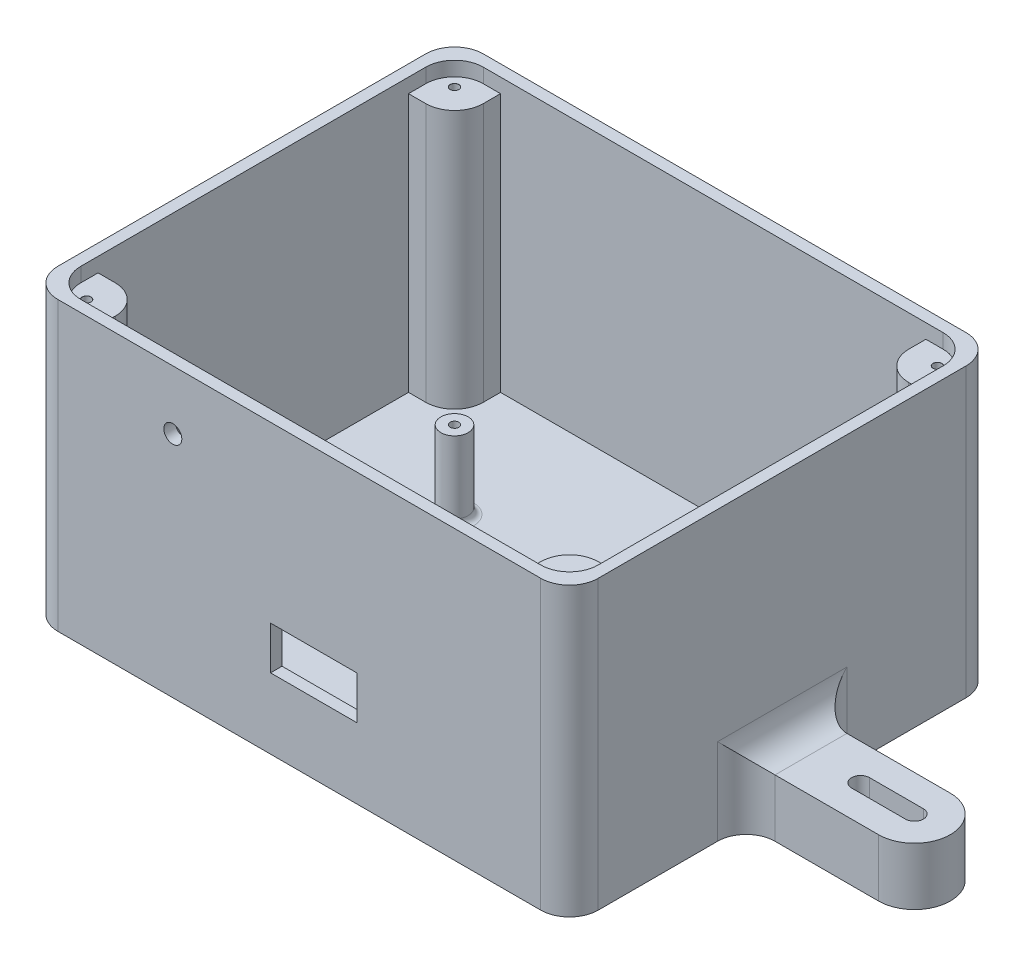
SolidWorks part; units mm, degrees
ref_plane "Plano frontal" through (0, 0, 0) normal (0, 0, 1) x (1, 0, 0)
ref_plane "Plano superior" through (0, 0, 0) normal (0, 1, 0) x (1, 0, 0)
ref_plane "Plano direito" through (0, 0, 0) normal (1, 0, 0) x (0, 0, -1)
ref_plane "Plano1" through (0, 0, -4.75) normal (0, 0, 1) x (1, 0, 0)
sketch "Esboço1" plane through (0, 0, -4.75) normal (0, 0, 1) x (1, 0, 0)
  line L0 (100, 27) -> (95.25, 27)
  line L1 (95.25, 27) -> (95.25, 26)
  line L2 (95.25, 26) -> (100, 26)
  line L3 (100, 26) -> (100, 27)
  line L4 (95.25, 27) -> (95.25, 26) construction
revolve "Revolução1" add sketch "Esboço1" angle 180 about L4 reverse direction yes
sketch "Esboço2" plane through (0, 0, -4.75) normal (0, 0, 1) x (1, 0, 0)
  line L0 (90.5, 100) -> (100, 100)
  line L1 (100, 100) -> (100, 26)
  line L2 (100, 26) -> (90.5, 26)
  line L3 (90.5, 26) -> (90.5, 100)
extrude "Ressalto-extrusão1" add sketch "Esboço2" along normal blind 8.75
sketch "Esboço3" plane through (90.5, 0, 0) normal (-1, 0, 0) x (0, 0, 1)
  line L0 (-4.75, 27) -> (4, 27)
  line L1 (4, 27) -> (4, 100)
  line L2 (4, 100) -> (-4.75, 100)
  line L3 (-4.75, 100) -> (-4.75, 27)
extrude "Corte-extrusão1" cut sketch "Esboço3" against normal blind 1.5
sketch "Esboço4" plane through (0, 0, -4.75) normal (0, 0, -1) x (-1, 0, 0)
  line L0 (-92, 27) -> (-92, 100)
  line L1 (-92, 100) -> (-100, 100)
  line L2 (-100, 100) -> (-100, 27)
  line L3 (-100, 27) -> (-92, 27)
extrude "Corte-extrusão2" cut sketch "Esboço4" against normal blind 4.75
sketch "Esboço5" plane through (92, 0, 0) normal (-1, 0, 0) x (0, 0, 1)
  line L0 (4, 32) -> (0, 32)
  line L1 (0, 32) -> (0, 100)
  line L2 (0, 100) -> (4, 100)
  line L3 (4, 100) -> (4, 32)
extrude "Ressalto-extrusão2" add sketch "Esboço5" along normal blind 52
sketch "Esboço6" plane through (40, 0, 0) normal (-1, 0, 0) x (0, 0, 1)
  line L0 (4, 26) -> (0, 26)
  line L1 (0, 26) -> (0, 100)
  line L2 (0, 100) -> (4, 100)
  line L3 (4, 100) -> (4, 26)
extrude "Ressalto-extrusão3" add sketch "Esboço6" along normal blind 80
sketch "Esboço7" plane through (100, 0, 0) normal (1, 0, 0) x (0, 0, -1)
  line L0 (0, 100) -> (0, 26)
  line L1 (0, 26) -> (-4, 26)
  line L2 (-4, 26) -> (-4, 100)
  line L3 (-4, 100) -> (0, 100)
extrude "Ressalto-extrusão4" add sketch "Esboço7" along normal blind 40
sketch "Esboço8" plane through (140, 0, 0) normal (1, 0, 0) x (0, 0, -1)
  line L0 (140, 26) -> (-4, 26)
  line L1 (-4, 26) -> (-4, 100)
  line L2 (-4, 100) -> (140, 100)
  line L3 (140, 100) -> (140, 26)
extrude "Ressalto-extrusão5" add sketch "Esboço8" along normal blind 4
sketch "Esboço9" plane through (-40, 0, 0) normal (-1, 0, 0) x (0, 0, 1)
  line L0 (-140, 26) -> (-140, 100)
  line L1 (-140, 100) -> (4, 100)
  line L2 (4, 100) -> (4, 26)
  line L3 (4, 26) -> (-140, 26)
extrude "Ressalto-extrusão6" add sketch "Esboço9" along normal blind 4
sketch "Esboço10" plane through (0, 0, -140) normal (0, 0, -1) x (-1, 0, 0)
  line L0 (-144, 26) -> (-144, 100)
  line L1 (-144, 100) -> (44, 100)
  line L2 (44, 100) -> (44, 26)
  line L3 (44, 26) -> (-144, 26)
extrude "Ressalto-extrusão7" add sketch "Esboço10" along normal blind 4
sketch "Esboço11" plane through (0, 26, 0) normal (0, -1, 0) x (1, 0, 0)
  line L0 (144, -144) -> (-44, -144)
  line L1 (-44, -144) -> (-44, 4)
  line L2 (-44, 4) -> (144, 4)
  line L3 (144, 4) -> (144, -144)
extrude "Ressalto-extrusão8" add sketch "Esboço11" along normal blind 26
sketch "Esboço12" plane through (0, 26, 0) normal (0, 1, 0) x (-1, 0, 0)
  line L0 (-140, -140) -> (40, -140)
  line L1 (40, -140) -> (40, 0)
  line L2 (40, 0) -> (-90.5, 0)
  line L3 (-90.5, 0) -> (-90.5, -4.75)
  line L4 (-100, -4.75) -> (-100, 0)
  line L5 (-100, 0) -> (-140, 0)
  line L6 (-140, 0) -> (-140, -140)
  arc A0 (-90.5, -4.75) -> (-100, -4.75) centre (-95.25, -4.75) cw
extrude "Corte-extrusão3" cut sketch "Esboço12" against normal blind 21
ref_plane "Plano2" through (0, 0, 0) normal (0, -1, 0) x (1, 0, 0)
sketch "Esboço13" plane through (0, 0, 0) normal (0, -1, 0) x (1, 0, 0)
  line L0 (144, -82.5) -> (190, -82.5)
  line L1 (190, -57.5) -> (144, -57.5)
  line L2 (144, -57.5) -> (144, -82.5)
  arc A0 (190, -82.5) -> (190, -57.5) centre (190, -70) ccw
extrude "Ressalto-extrusão9" add sketch "Esboço13" against normal blind 20
sketch "Esboço14" plane through (0, 0, 0) normal (0, -1, 0) x (1, 0, 0)
  line L0 (190, -66.875) -> (171.25, -66.875)
  line L1 (171.25, -73.125) -> (190, -73.125)
  arc A0 (190, -73.125) -> (190, -66.875) centre (190, -70) ccw
  arc A1 (171.25, -66.875) -> (171.25, -73.125) centre (171.25, -70) ccw
extrude "Corte-extrusão4" cut sketch "Esboço14" against normal through all
sketch "Esboço15" plane through (0, 0, 0) normal (0, -1, 0) x (1, 0, 0)
  line L0 (-44, -57.5) -> (-90, -57.5)
  line L1 (-90, -82.5) -> (-44, -82.5)
  line L2 (-44, -82.5) -> (-44, -57.5)
  arc A0 (-90, -57.5) -> (-90, -82.5) centre (-90, -70) ccw
extrude "Ressalto-extrusão10" add sketch "Esboço15" against normal blind 20
sketch "Esboço16" plane through (0, 20, 0) normal (0, 1, 0) x (-1, 0, 0)
  line L0 (71.25, -73.125) -> (90, -73.125)
  line L1 (90, -66.875) -> (71.25, -66.875)
  arc A0 (71.25, -66.875) -> (71.25, -73.125) centre (71.25, -70) ccw
  arc A1 (90, -73.125) -> (90, -66.875) centre (90, -70) ccw
extrude "Corte-extrusão5" cut sketch "Esboço16" against normal through all
sketch "Esboço17" plane through (0, 5, 0) normal (0, 1, 0) x (-1, 0, 0)
  line L0 (24, -124) -> (40, -124)
  line L1 (40, -124) -> (40, -140)
  line L2 (40, -140) -> (24, -140)
  line L3 (24, -140) -> (24, -124)
extrude "Ressalto-extrusão11" add sketch "Esboço17" along normal blind 90
sketch "Esboço18" plane through (0, 5, 0) normal (0, 1, 0) x (-1, 0, 0)
  line L0 (-124, -140) -> (-140, -140)
  line L1 (-140, -140) -> (-140, -124)
  line L2 (-140, -124) -> (-124, -124)
  line L3 (-124, -124) -> (-124, -140)
extrude "Ressalto-extrusão12" add sketch "Esboço18" along normal blind 90
sketch "Esboço19" plane through (0, 5, 0) normal (0, 1, 0) x (-1, 0, 0)
  line L0 (-124, -16) -> (-140, -16)
  line L1 (-140, -16) -> (-140, 0)
  line L2 (-140, 0) -> (-124, 0)
  line L3 (-124, 0) -> (-124, -16)
extrude "Ressalto-extrusão13" add sketch "Esboço19" along normal blind 90
sketch "Esboço20" plane through (0, 5, 0) normal (0, 1, 0) x (-1, 0, 0)
  line L0 (24, -16) -> (24, 0)
  line L1 (24, 0) -> (40, 0)
  line L2 (40, 0) -> (40, -16)
  line L3 (40, -16) -> (24, -16)
extrude "Ressalto-extrusão14" add sketch "Esboço20" along normal blind 90
sketch "Esboço21" plane through (0, 5, 0) normal (0, 1, 0) x (-1, 0, 0)
  line L0 (-9.5, -4.75) -> (-9.5, 0)
  line L1 (-9.5, 0) -> (0, 0)
  line L2 (0, 0) -> (0, -4.75)
  arc A0 (0, -4.75) -> (-9.5, -4.75) centre (-4.75, -4.75) cw
extrude "Ressalto-extrusão15" add sketch "Esboço21" along normal blind 22
ref_plane "Plano3" through (0, 0, -95.25) normal (0, 0, 1) x (1, 0, 0)
sketch "Esboço22" plane through (0, 0, -95.25) normal (0, 0, 1) x (1, 0, 0)
  line L0 (9.5, 27) -> (4.75, 27)
  line L1 (4.75, 27) -> (4.75, 5)
  line L2 (4.75, 5) -> (9.5, 5)
  line L3 (9.5, 5) -> (9.5, 27)
  line L4 (4.75, 27) -> (4.75, 5) construction
revolve "Revolução2" add sketch "Esboço22" angle 360 about L4 reverse direction yes
hole_wizard "Furo de diâmetro Ø3.0 (3)1" positions "Esboço24" profile "Esboço23" hole size "Ø3.0" standard "Ansi Metric"
sketch "Esboço24" plane through (0, 95, 0) normal (0, 1, 0) x (1, 0, 0)
  point P0 (-34, 6)
  point P1 (134, 6)
  point P2 (134, 134)
  point P3 (-34, 134)
sketch "Esboço23" plane through (-34, 95, -6) normal (1, 0, 0) x (0, 0, 1)
  line L0 (0, 0) -> (0, 15.9013)
  line L1 (0, 15.9013) -> (1.5, 15)
  line L2 (1.5, 15) -> (1.5, 0)
  line L5 (1.5, 0) -> (0, 0)
  line L10 (0, 15.9013) -> (-1.5, 15) construction
  line L11 (0, -6.35) -> (0, 107.95) construction
  dimension "Hole Dia." = 3
  dimension "Hole Depth" = 15
  dimension "Drill Angle" = 118
hole_wizard "Furo de diâmetro Ø3.0 (3)2" positions "Esboço26" profile "Esboço25" hole size "Ø3.0" standard "Ansi Metric"
sketch "Esboço26" plane through (0, 27, 0) normal (0, 1, 0) x (1, 0, 0)
  point P0 (95.25, 4.75)
  point P1 (4.75, 4.75)
  point P2 (4.75, 95.25)
sketch "Esboço25" plane through (95.25, 27, -4.75) normal (1, 0, 0) x (0, 0, 1)
  line L0 (0, 0) -> (0, 15.9013)
  line L1 (0, 15.9013) -> (1.5, 15)
  line L2 (1.5, 15) -> (1.5, 0)
  line L5 (1.5, 0) -> (0, 0)
  line L10 (0, 15.9013) -> (-1.5, 15) construction
  line L11 (0, -6.35) -> (0, 107.95) construction
  dimension "Hole Dia." = 3
  dimension "Hole Depth" = 15
  dimension "Drill Angle" = 118
hole_wizard "Broca de rosquear para helicoide M61" positions "Esboço28" profile "Esboço27" hole size "M6x1.0" standard "Ansi Metric"
sketch "Esboço28" plane through (0, 0, 4) normal (0, 0, 1) x (1, 0, 0)
  point P0 (6, 79.5)
sketch "Esboço27" plane through (6, 79.5, 4) normal (1, 0, 0) x (0, -1, 0)
  line L0 (0, 0) -> (0, 4)
  line L1 (0, 4) -> (3.125, 4)
  line L2 (3.125, 4) -> (3.125, 0)
  line L5 (3.125, 0) -> (0, 0)
  line L11 (0, -6.35) -> (0, 107.95) construction
  dimension "Thru Hole Dia." = 6.25
  dimension "Thru Hole Depth" = 4
chamfer "Chanfro1" distance 0.025 angle 45 7 edges at (95.25, 27, -3.25) (4.75, 27, -93.75) (134, 95, -4.5) (-34, 95, -4.5) (4.75, 27, -3.25) (134, 95, -132.5) (-34, 95, -132.5)
fillet "Filete1" radius 2 3 edges at (92, 32, 2) (40, 26, 2) (40, 32, 2) tangent propagation no
fillet "Filete2" radius 10 18 edges at (124, 50, -124) (-44, 10, -82.5) (-44, 20, -70) (-44, 10, -57.5) (144, 10, -82.5) (144, 10, -57.5) (144, 20, -70) (140, 97.5, -140) (140, 97.5, 0) (-24, 50, -16) (-40, 97.5, 0) (-40, 97.5, -140) (144, 50, -144) (-24, 50, -124) (-44, 50, -144) (124, 50, -16) (-44, 50, 4) (144, 50, 4) tangent propagation no
sketch "Esboço35" plane through (0, 0, -95.25) normal (0, 0, 1) x (1, 0, 0)
  line L0 (100, 27) -> (95.25, 27)
  line L1 (95.25, 27) -> (95.25, 5)
  line L2 (95.25, 5) -> (100, 5)
  line L3 (100, 5) -> (100, 27)
  line L4 (95.25, 27) -> (95.25, 5) construction
revolve "Revolução3" add sketch "Esboço35" angle 360 about L1 reverse direction yes
sketch "Esboço42" plane through (0, 0, -95.25) normal (0, 0, 1) x (1, 0, 0)
  line L0 (96.775, 27) -> (95.25, 27)
  line L1 (95.25, 27) -> (95.25, 11.0987)
  line L2 (95.25, 11.0987) -> (96.75, 12)
  line L3 (96.75, 12) -> (96.75, 26.975)
  line L4 (96.75, 26.975) -> (96.775, 27)
  line L5 (95.25, 27) -> (95.25, 11.0987) construction
revolve "Corte-Revolução1" cut sketch "Esboço42" angle 360 about L1 reverse direction yes
fillet "Filete3" radius 2 8 edges at (0, 5, -2.375) (9.5, 5, -2.375) (4.75, 5, -9.5) (100, 5, -2.375) (95.25, 5, -9.5) (90.5, 5, -2.375) (95.25, 5, -100) (4.75, 5, -100)
sketch "Esboço43" plane through (0, 0, 4) normal (0, 0, 1) x (1, 0, 0)
  line L0 (42, 32) -> (40, 32) construction
  line L1 (90, 32) -> (92, 32) construction
  line L2 (42, 26) -> (40, 26) construction
  line L4 (40, 26) -> (92, 26)
  line L5 (40, 26) -> (40, 32)
  line L6 (40, 32) -> (92, 32)
  line L7 (92, 26) -> (92, 32)
extrude "Ressalto-extrusão16" add sketch "Esboço43" against normal blind 4
sketch "Esboço44" plane through (0, 27, 0) normal (0, 1, 0) x (-1, 0, 0)
  line L0 (-9.5, -4.75) -> (-9.5, 0)
  line L1 (-9.5, 0) -> (0, 0)
  line L2 (0, 0) -> (0, -4.75)
  line L3 (-100, 0) -> (-100, -4.75)
  line L4 (-90.5, 0) -> (-100, 0)
  line L5 (-90.5, -4.75) -> (-90.5, 0)
  circle A0 centre (-4.75, -95.25) radius 4.75
  circle A1 centre (-95.25, -95.25) radius 4.75
  arc A2 (-9.5, -4.75) -> (0, -4.75) centre (-4.75, -4.75) ccw
  circle A3 centre (-4.75, -95.25) radius 1.525
  circle A4 centre (-95.25, -95.25) radius 1.525
  circle A5 centre (-4.75, -4.75) radius 1.525
  circle A6 centre (-95.25, -4.75) radius 1.525
  arc A7 (-90.5, -4.75) -> (-100, -4.75) centre (-95.25, -4.75) cw
extrude "Ressalto-extrusão17" add sketch "Esboço44" along normal mid plane 10
sketch "Esboço47" plane through (0, 0, 4) normal (0, 0, 1) x (1, 0, 0)
  line L0 (100, 32) -> (40, 32) construction
  line L1 (0, 32) -> (100, 32) construction
  line L3 (40, 39.5) -> (70, 39.5)
  line L4 (40, 39.5) -> (40, 24.5)
  line L5 (40, 24.5) -> (70, 24.5)
  line L6 (70, 39.5) -> (70, 24.5)
  point P9 (40, 32)
  dimension "D1" = 60
  dimension "D2" = 30
  dimension "D3" = 15
extrude "Corte-extrusão7" cut sketch "Esboço47" against normal blind 10
